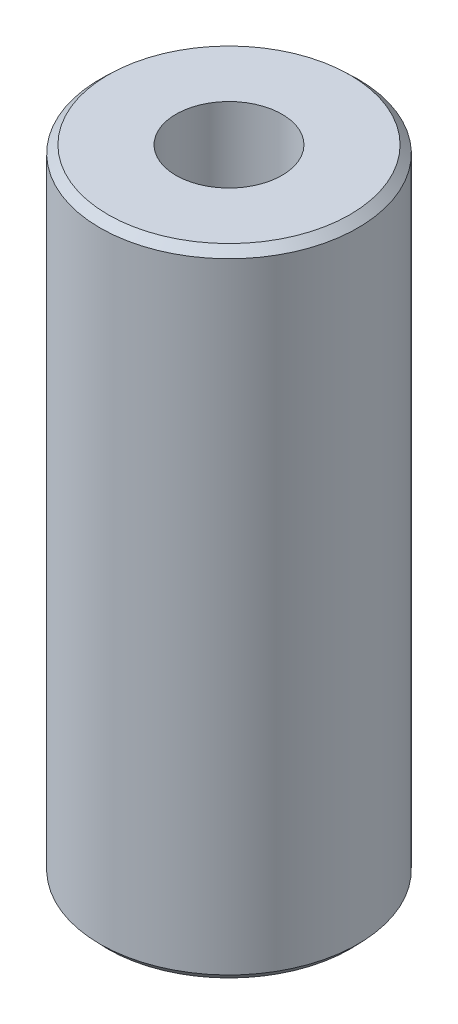
SolidWorks part; units mm, degrees
ref_plane "Front Plane" through (0, 0, 0) normal (0, 0, 1) x (1, 0, 0)
ref_plane "Top Plane" through (0, 0, 0) normal (0, 1, 0) x (1, 0, 0)
ref_plane "Right Plane" through (0, 0, 0) normal (1, 0, 0) x (0, 0, -1)
sketch "Sketch1" plane through (0, 0, 0) normal (0, 1, 0) x (1, 0, 0)
  circle A0 centre (0, 0) radius 60
  dimension "SHAFT_OD" = 120
extrude "Boss-Extrude1" add sketch "Sketch1" along normal blind 295.8572
sketch "Sketch2" plane through (0, 0, 0) normal (0, 1, 0) x (1, 0, 0)
  circle A0 centre (0, 0) radius 24.675
  dimension "BORE_D" = 49.3499
extrude "Cut-Extrude1" cut sketch "Sketch2" along normal through all
chamfer "Chamfer1" distance 3.5139 angle 46.447 2 edges at (0, 295.8572, 60) (0, 0, 60) first distance on face at (0, 295.8572, 60) first distance on face at (0, 0, 24.675)
